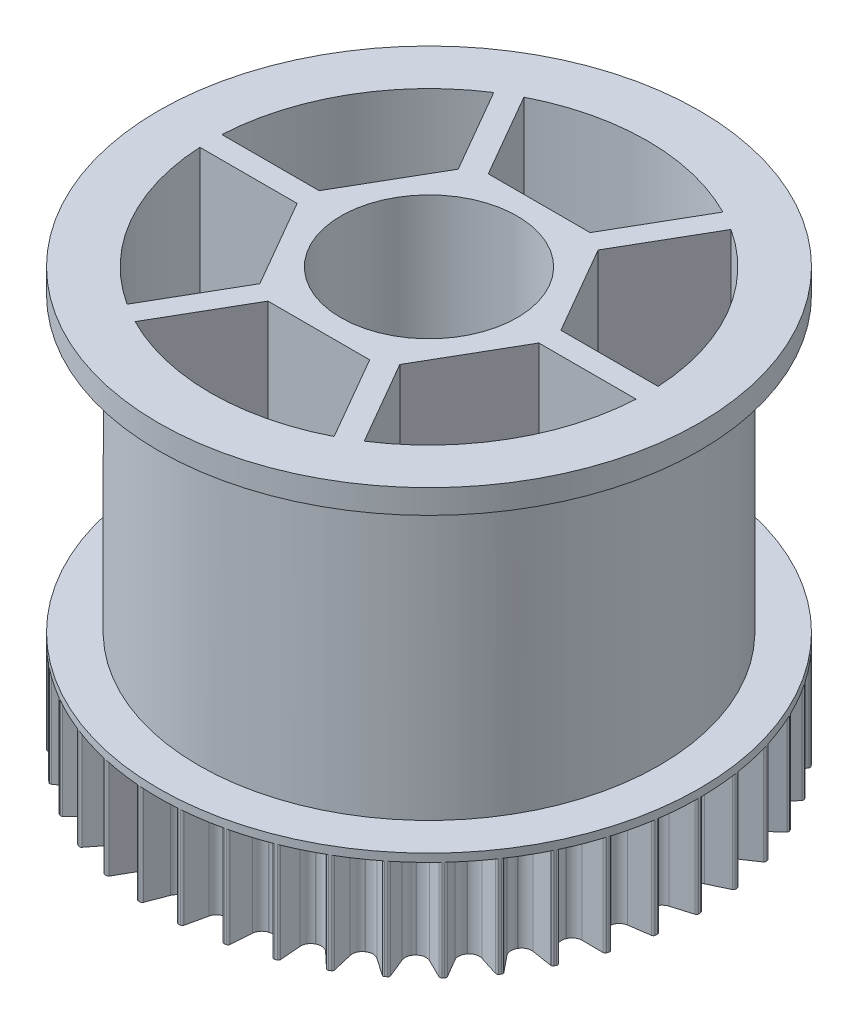
SolidWorks part; units mm, degrees
ref_plane "前视基准面" through (0, 0, 0) normal (0, 0, 1) x (1, 0, 0)
ref_plane "上视基准面" through (0, 0, 0) normal (0, 1, 0) x (1, 0, 0)
ref_plane "右视基准面" through (0, 0, 0) normal (1, 0, 0) x (0, 0, -1)
other "Configuration Table"
sketch "草图1" plane through (0, 0, 0) normal (0, 1, 0) x (1, 0, 0)
  line L0 (0, 0) -> (7.9279, 0) construction
  line L1 (0, 0) -> (0, 4.4256) construction
  line L2 (12.4216, 0.4494) -> (13.4287, 0.1463)
  line L3 (12.4216, -0.4494) -> (13.4287, -0.1463)
  line L4 (12.2159, -2.2957) -> (13.2569, -2.1461)
  line L5 (12.3499, -1.407) -> (13.3005, -1.8568)
  line L6 (11.7373, -4.0908) -> (12.789, -4.098)
  line L7 (12.0023, -3.2319) -> (12.8752, -3.8184)
  line L8 (10.9965, -5.7945) -> (12.0354, -5.9583)
  line L9 (11.3865, -4.9846) -> (12.1623, -5.6947)
  line L10 (10.0101, -7.3687) -> (11.0129, -7.6855)
  line L11 (10.5164, -6.626) -> (11.1777, -7.4438)
  line L12 (8.8, -8.7783) -> (9.7445, -9.2411)
  line L13 (9.4114, -8.1194) -> (9.9434, -9.0266)
  line L14 (7.3934, -9.9918) -> (8.2583, -10.5902)
  line L15 (8.0961, -9.4314) -> (8.487, -10.4078)
  line L16 (5.8216, -10.9822) -> (6.5877, -11.7028)
  line L17 (6.6, -10.5328) -> (6.841, -11.5565)
  line L18 (4.1198, -11.7272) -> (4.7699, -12.5539)
  line L19 (4.9565, -11.3988) -> (5.0422, -12.447)
  line L20 (2.3259, -12.2102) -> (2.8456, -13.1246)
  line L21 (3.2022, -12.0102) -> (3.1308, -13.0595)
  line L22 (0.4801, -12.4205) -> (0.8577, -13.4021)
  line L23 (1.3764, -12.3533) -> (1.1494, -13.3802)
  line L24 (-1.3764, -12.3533) -> (-1.1494, -13.3802)
  line L25 (-0.4801, -12.4205) -> (-0.8577, -13.4021)
  line L26 (-3.2022, -12.0102) -> (-3.1308, -13.0595)
  line L27 (-2.3259, -12.2102) -> (-2.8456, -13.1246)
  line L28 (-4.9565, -11.3988) -> (-5.0422, -12.447)
  line L29 (-4.1198, -11.7272) -> (-4.7699, -12.5539)
  line L30 (-6.6, -10.5328) -> (-6.841, -11.5565)
  line L31 (-5.8216, -10.9822) -> (-6.5877, -11.7028)
  line L32 (-8.0961, -9.4314) -> (-8.487, -10.4078)
  line L33 (-7.3934, -9.9918) -> (-8.2583, -10.5902)
  line L34 (-9.4114, -8.1194) -> (-9.9434, -9.0266)
  line L35 (-8.8, -8.7783) -> (-9.7445, -9.2411)
  line L36 (-10.5164, -6.626) -> (-11.1777, -7.4438)
  line L37 (-10.0101, -7.3687) -> (-11.0129, -7.6855)
  line L38 (-11.3865, -4.9846) -> (-12.1623, -5.6947)
  line L39 (-10.9965, -5.7945) -> (-12.0354, -5.9583)
  line L40 (-12.0023, -3.2319) -> (-12.8752, -3.8184)
  line L41 (-11.7373, -4.0908) -> (-12.789, -4.098)
  line L42 (-12.3499, -1.407) -> (-13.3005, -1.8568)
  line L43 (-12.2159, -2.2957) -> (-13.2569, -2.1461)
  line L44 (-12.4216, 0.4494) -> (-13.4287, 0.1463)
  line L45 (-12.4216, -0.4494) -> (-13.4287, -0.1463)
  line L46 (-12.2159, 2.2957) -> (-13.2569, 2.1461)
  line L47 (-12.3499, 1.407) -> (-13.3005, 1.8568)
  line L48 (-11.7373, 4.0908) -> (-12.789, 4.098)
  line L49 (-12.0023, 3.2319) -> (-12.8752, 3.8184)
  line L50 (-10.9965, 5.7945) -> (-12.0354, 5.9583)
  line L51 (-11.3865, 4.9846) -> (-12.1623, 5.6947)
  line L52 (-10.0101, 7.3687) -> (-11.0129, 7.6855)
  line L53 (-10.5164, 6.626) -> (-11.1777, 7.4438)
  line L54 (-8.8, 8.7783) -> (-9.7445, 9.2411)
  line L55 (-9.4114, 8.1194) -> (-9.9434, 9.0266)
  line L56 (-7.3934, 9.9918) -> (-8.2583, 10.5902)
  line L57 (-8.0961, 9.4314) -> (-8.487, 10.4078)
  line L58 (-5.8216, 10.9822) -> (-6.5877, 11.7028)
  line L59 (-6.6, 10.5328) -> (-6.841, 11.5565)
  line L60 (-4.1198, 11.7272) -> (-4.7699, 12.5539)
  line L61 (-4.9565, 11.3988) -> (-5.0422, 12.447)
  line L62 (-2.3259, 12.2102) -> (-2.8456, 13.1246)
  line L63 (-3.2022, 12.0102) -> (-3.1308, 13.0595)
  line L64 (-0.4801, 12.4205) -> (-0.8577, 13.4021)
  line L65 (-1.3764, 12.3533) -> (-1.1494, 13.3802)
  line L66 (1.3764, 12.3533) -> (1.1494, 13.3802)
  line L67 (0.4801, 12.4205) -> (0.8577, 13.4021)
  line L68 (3.2022, 12.0102) -> (3.1308, 13.0595)
  line L69 (2.3259, 12.2102) -> (2.8456, 13.1246)
  line L70 (4.9565, 11.3988) -> (5.0422, 12.447)
  line L71 (4.1198, 11.7272) -> (4.7699, 12.5539)
  line L72 (6.6, 10.5328) -> (6.841, 11.5565)
  line L73 (5.8216, 10.9822) -> (6.5877, 11.7028)
  line L74 (8.0961, 9.4314) -> (8.487, 10.4078)
  line L75 (7.3934, 9.9918) -> (8.2583, 10.5902)
  line L76 (9.4114, 8.1194) -> (9.9434, 9.0266)
  line L77 (8.8, 8.7783) -> (9.7445, 9.2411)
  line L78 (10.5164, 6.626) -> (11.1777, 7.4438)
  line L79 (10.0101, 7.3687) -> (11.0129, 7.6855)
  line L80 (11.3865, 4.9846) -> (12.1623, 5.6947)
  line L81 (10.9965, 5.7945) -> (12.0354, 5.9583)
  line L82 (12.0023, 3.2319) -> (12.8752, 3.8184)
  line L83 (11.7373, 4.0908) -> (12.789, 4.098)
  line L84 (12.3499, 1.407) -> (13.3005, 1.8568)
  line L85 (12.2159, 2.2957) -> (13.2569, 2.1461)
  line L95 (3.1754, 5.5) -> (-3.1754, 5.5) construction
  line L96 (3.1754, 5.5) -> (6.0333, 0.55) construction
  line L97 (0, 0) -> (3.1754, 5.5) construction
  line L98 (-3.1754, 5.5) -> (-6.0333, 0.55) construction
  line L99 (3.493, -4.95) -> (6.0333, -0.55)
  line L100 (2.5403, -5.5) -> (-2.5403, -5.5)
  line L101 (-3.493, -4.95) -> (-6.0333, -0.55)
  line L102 (8.1752, 0) -> (11.2, 0) construction
  line L103 (6.0333, 0.55) -> (11.1865, 0.55)
  line L104 (6.0333, -0.55) -> (11.1865, -0.55)
  line L105 (3.493, -4.95) -> (6.0696, -9.4128)
  line L106 (2.5403, -5.5) -> (5.1169, -9.9628)
  line L107 (-2.5403, -5.5) -> (-5.1169, -9.9628)
  line L108 (-3.493, -4.95) -> (-6.0696, -9.4128)
  line L109 (-6.0333, -0.55) -> (-11.1865, -0.55)
  line L110 (-6.0333, 0.55) -> (-11.1865, 0.55)
  line L111 (-3.493, 4.95) -> (-6.0696, 9.4128)
  line L112 (-2.5403, 5.5) -> (-5.1169, 9.9628)
  line L113 (2.5403, 5.5) -> (5.1169, 9.9628)
  line L114 (3.493, 4.95) -> (6.0696, 9.4128)
  line L115 (0, 0) -> (12.0337, 1.2648) construction
  line L116 (12.0337, -1.2648) -> (0, 0) construction
  line L117 (-6.0333, 0.55) -> (-3.493, 4.95)
  line L118 (-2.5403, 5.5) -> (2.5403, 5.5)
  line L119 (3.493, 4.95) -> (6.0333, 0.55)
  circle A0 centre (0, 0) radius 11.2 construction
  circle A1 centre (0, 0) radius 12.1 construction
  circle A2 centre (0, 0) radius 13.5 construction
  arc A3 (13.4999, 0.0509) -> (13.4999, -0.0509) centre (0, 0) cw
  arc A4 (12.0671, 0.8914) -> (12.0337, 1.2648) centre (0, 0) ccw construction
  arc A5 (13.4287, -0.1463) -> (13.4999, -0.0509) centre (13.3999, -0.0505) ccw
  arc A6 (13.4287, 0.1463) -> (13.4999, 0.0509) centre (13.3999, 0.0505) cw
  arc A7 (12.0671, -0.8914) -> (12.0337, -1.2648) centre (0, 0) cw construction
  arc A8 (12.4216, -0.4494) -> (12.0671, -0.8914) centre (12.5658, -0.9282) ccw
  arc A9 (12.4216, 0.4494) -> (12.0671, 0.8914) centre (12.5658, 0.9282) cw
  arc A10 (12.2159, -2.2957) -> (11.7995, -2.6799) centre (12.2871, -2.7907) ccw
  arc A11 (12.3499, -1.407) -> (12.0652, -0.9171) centre (12.5638, -0.955) cw
  arc A12 (13.3005, -1.8568) -> (13.3567, -1.9617) centre (13.2578, -1.9472) cw
  arc A13 (13.3567, -1.9617) -> (13.3415, -2.0624) centre (0, 0) cw
  arc A14 (13.2569, -2.1461) -> (13.3415, -2.0624) centre (13.2427, -2.0471) ccw
  arc A15 (11.7373, -4.0908) -> (11.2683, -4.4086) centre (11.7339, -4.5908) ccw
  arc A16 (12.0023, -3.2319) -> (11.7937, -2.7051) centre (12.2811, -2.8169) cw
  arc A17 (12.8752, -3.8184) -> (12.9151, -3.9305) centre (12.8195, -3.9014) cw
  arc A18 (12.9151, -3.9305) -> (12.8851, -4.0278) centre (0, 0) cw
  arc A19 (12.789, -4.098) -> (12.8851, -4.0278) centre (12.7897, -3.998) ccw
  arc A20 (10.9965, -5.7945) -> (10.4854, -6.0388) centre (10.9186, -6.2884) ccw
  arc A21 (11.3865, -4.9846) -> (11.2589, -4.4326) centre (11.7241, -4.6158) cw
  arc A22 (12.1623, -5.6947) -> (12.1851, -5.8115) centre (12.0948, -5.7685) cw
  arc A23 (12.1851, -5.8115) -> (12.1409, -5.9032) centre (0, 0) cw
  arc A24 (12.0354, -5.9583) -> (12.1409, -5.9032) centre (12.051, -5.8595) ccw
  arc A25 (10.0101, -7.3687) -> (9.4682, -7.5341) centre (9.8595, -7.8455) ccw
  arc A26 (10.5164, -6.626) -> (10.4724, -6.0612) centre (10.9052, -6.3116) cw
  arc A27 (11.1777, -7.4438) -> (11.1828, -7.5627) centre (11.1, -7.5067) cw
  arc A28 (11.1828, -7.5627) -> (11.1255, -7.6468) centre (0, 0) cw
  arc A29 (11.0129, -7.6855) -> (11.1255, -7.6468) centre (11.0431, -7.5902) ccw
  arc A30 (8.8, -8.7783) -> (8.2395, -8.8611) centre (8.58, -9.2273) ccw
  arc A31 (9.4114, -8.1194) -> (9.4521, -7.5543) centre (9.8427, -7.8665) cw
  arc A32 (9.9434, -9.0266) -> (9.9308, -9.145) centre (9.8572, -9.0772) cw
  arc A33 (9.9308, -9.145) -> (9.8615, -9.2196) centre (0, 0) cw
  arc A34 (9.7445, -9.2411) -> (9.8615, -9.2196) centre (9.7885, -9.1513) ccw
  arc A35 (7.3934, -9.9918) -> (6.8268, -9.9902) centre (7.1089, -10.403) ccw
  arc A36 (8.0961, -9.4314) -> (8.2206, -8.8787) centre (8.5603, -9.2456) cw
  arc A37 (8.487, -10.4078) -> (8.4568, -10.5229) centre (8.3942, -10.445) cw
  arc A38 (8.4568, -10.5229) -> (8.3773, -10.5864) centre (0, 0) cw
  arc A39 (8.2583, -10.5902) -> (8.3773, -10.5864) centre (8.3152, -10.508) ccw
  arc A40 (5.8216, -10.9822) -> (5.2616, -10.8961) centre (5.479, -11.3464) ccw
  arc A41 (6.6, -10.5328) -> (6.8055, -10.0048) centre (7.0867, -10.4182) cw
  arc A42 (6.841, -11.5565) -> (6.794, -11.6658) centre (6.7437, -11.5794) cw
  arc A43 (6.794, -11.6658) -> (6.7059, -11.7167) centre (0, 0) cw
  arc A44 (6.5877, -11.7028) -> (6.7059, -11.7167) centre (6.6562, -11.6299) ccw
  arc A45 (4.1198, -11.7272) -> (3.5789, -11.5586) centre (3.7268, -12.0362) ccw
  arc A46 (4.9565, -11.3988) -> (5.2384, -10.9073) centre (5.4548, -11.358) cw
  arc A47 (5.0422, -12.447) -> (4.9795, -12.5481) centre (4.9426, -12.4552) cw
  arc A48 (4.9795, -12.5481) -> (4.8847, -12.5853) centre (0, 0) cw
  arc A49 (4.7699, -12.5539) -> (4.8847, -12.5853) centre (4.8485, -12.4921) ccw
  arc A50 (2.3259, -12.2102) -> (1.8162, -11.9629) centre (1.8912, -12.4573) ccw
  arc A51 (3.2022, -12.0102) -> (3.5542, -11.5662) centre (3.7011, -12.0442) cw
  arc A52 (3.1308, -13.0595) -> (3.0536, -13.1501) centre (3.031, -13.0527) cw
  arc A53 (3.0536, -13.1501) -> (2.9544, -13.1728) centre (0, 0) cw
  arc A54 (2.8456, -13.1246) -> (2.9544, -13.1728) centre (2.9325, -13.0752) ccw
  arc A55 (0.4801, -12.4205) -> (0.0129, -12.1) centre (0.0134, -12.6) ccw
  arc A56 (1.3764, -12.3533) -> (1.7906, -11.9668) centre (1.8646, -12.4613) cw
  arc A57 (1.1494, -13.3802) -> (1.0596, -13.4584) centre (1.0518, -13.3587) cw
  arc A58 (1.0596, -13.4584) -> (0.9581, -13.466) centre (0, 0) cw
  arc A59 (0.8577, -13.4021) -> (0.9581, -13.466) centre (0.951, -13.3662) ccw
  arc A60 (-1.3764, -12.3533) -> (-1.7906, -11.9668) centre (-1.8646, -12.4613) ccw
  arc A61 (-0.4801, -12.4205) -> (-0.0129, -12.1) centre (-0.0134, -12.6) cw
  arc A62 (-0.8577, -13.4021) -> (-0.9581, -13.466) centre (-0.951, -13.3662) cw
  arc A63 (-0.9581, -13.466) -> (-1.0596, -13.4584) centre (0, 0) cw
  arc A64 (-1.1494, -13.3802) -> (-1.0596, -13.4584) centre (-1.0518, -13.3587) ccw
  arc A65 (-3.2022, -12.0102) -> (-3.5542, -11.5662) centre (-3.7011, -12.0442) ccw
  arc A66 (-2.3259, -12.2102) -> (-1.8162, -11.9629) centre (-1.8912, -12.4573) cw
  arc A67 (-2.8456, -13.1246) -> (-2.9544, -13.1728) centre (-2.9325, -13.0752) cw
  arc A68 (-2.9544, -13.1728) -> (-3.0536, -13.1501) centre (0, 0) cw
  arc A69 (-3.1308, -13.0595) -> (-3.0536, -13.1501) centre (-3.031, -13.0527) ccw
  arc A70 (-4.9565, -11.3988) -> (-5.2384, -10.9073) centre (-5.4548, -11.358) ccw
  arc A71 (-4.1198, -11.7272) -> (-3.5789, -11.5586) centre (-3.7268, -12.0362) cw
  arc A72 (-4.7699, -12.5539) -> (-4.8847, -12.5853) centre (-4.8485, -12.4921) cw
  arc A73 (-4.8847, -12.5853) -> (-4.9795, -12.5481) centre (0, 0) cw
  arc A74 (-5.0422, -12.447) -> (-4.9795, -12.5481) centre (-4.9426, -12.4552) ccw
  arc A75 (-6.6, -10.5328) -> (-6.8055, -10.0048) centre (-7.0867, -10.4182) ccw
  arc A76 (-5.8216, -10.9822) -> (-5.2616, -10.8961) centre (-5.479, -11.3464) cw
  arc A77 (-6.5877, -11.7028) -> (-6.7059, -11.7167) centre (-6.6562, -11.6299) cw
  arc A78 (-6.7059, -11.7167) -> (-6.794, -11.6658) centre (0, 0) cw
  arc A79 (-6.841, -11.5565) -> (-6.794, -11.6658) centre (-6.7437, -11.5794) ccw
  arc A80 (-8.0961, -9.4314) -> (-8.2206, -8.8787) centre (-8.5603, -9.2456) ccw
  arc A81 (-7.3934, -9.9918) -> (-6.8268, -9.9902) centre (-7.1089, -10.403) cw
  arc A82 (-8.2583, -10.5902) -> (-8.3773, -10.5864) centre (-8.3152, -10.508) cw
  arc A83 (-8.3773, -10.5864) -> (-8.4568, -10.5229) centre (0, 0) cw
  arc A84 (-8.487, -10.4078) -> (-8.4568, -10.5229) centre (-8.3942, -10.445) ccw
  arc A85 (-9.4114, -8.1194) -> (-9.4521, -7.5543) centre (-9.8427, -7.8665) ccw
  arc A86 (-8.8, -8.7783) -> (-8.2395, -8.8611) centre (-8.58, -9.2273) cw
  arc A87 (-9.7445, -9.2411) -> (-9.8615, -9.2196) centre (-9.7885, -9.1513) cw
  arc A88 (-9.8615, -9.2196) -> (-9.9308, -9.145) centre (0, 0) cw
  arc A89 (-9.9434, -9.0266) -> (-9.9308, -9.145) centre (-9.8572, -9.0772) ccw
  arc A90 (-10.5164, -6.626) -> (-10.4724, -6.0612) centre (-10.9052, -6.3116) ccw
  arc A91 (-10.0101, -7.3687) -> (-9.4682, -7.5341) centre (-9.8595, -7.8455) cw
  arc A92 (-11.0129, -7.6855) -> (-11.1255, -7.6468) centre (-11.0431, -7.5902) cw
  arc A93 (-11.1255, -7.6468) -> (-11.1828, -7.5627) centre (0, 0) cw
  arc A94 (-11.1777, -7.4438) -> (-11.1828, -7.5627) centre (-11.1, -7.5067) ccw
  arc A95 (-11.3865, -4.9846) -> (-11.2589, -4.4326) centre (-11.7241, -4.6158) ccw
  arc A96 (-10.9965, -5.7945) -> (-10.4854, -6.0388) centre (-10.9186, -6.2884) cw
  arc A97 (-12.0354, -5.9583) -> (-12.1409, -5.9032) centre (-12.051, -5.8595) cw
  arc A98 (-12.1409, -5.9032) -> (-12.1851, -5.8115) centre (0, 0) cw
  arc A99 (-12.1623, -5.6947) -> (-12.1851, -5.8115) centre (-12.0948, -5.7685) ccw
  arc A100 (-12.0023, -3.2319) -> (-11.7937, -2.7051) centre (-12.2811, -2.8169) ccw
  arc A101 (-11.7373, -4.0908) -> (-11.2683, -4.4086) centre (-11.7339, -4.5908) cw
  arc A102 (-12.789, -4.098) -> (-12.8851, -4.0278) centre (-12.7897, -3.998) cw
  arc A103 (-12.8851, -4.0278) -> (-12.9151, -3.9305) centre (0, 0) cw
  arc A104 (-12.8752, -3.8184) -> (-12.9151, -3.9305) centre (-12.8195, -3.9014) ccw
  arc A105 (-12.3499, -1.407) -> (-12.0652, -0.9171) centre (-12.5638, -0.955) ccw
  arc A106 (-12.2159, -2.2957) -> (-11.7995, -2.6799) centre (-12.2871, -2.7907) cw
  arc A107 (-13.2569, -2.1461) -> (-13.3415, -2.0624) centre (-13.2427, -2.0471) cw
  arc A108 (-13.3415, -2.0624) -> (-13.3567, -1.9617) centre (0, 0) cw
  arc A109 (-13.3005, -1.8568) -> (-13.3567, -1.9617) centre (-13.2578, -1.9472) ccw
  arc A110 (-12.4216, 0.4494) -> (-12.0671, 0.8914) centre (-12.5658, 0.9282) ccw
  arc A111 (-12.4216, -0.4494) -> (-12.0671, -0.8914) centre (-12.5658, -0.9282) cw
  arc A112 (-13.4287, -0.1463) -> (-13.4999, -0.0509) centre (-13.3999, -0.0505) cw
  arc A113 (-13.4999, -0.0509) -> (-13.4999, 0.0509) centre (0, 0) cw
  arc A114 (-13.4287, 0.1463) -> (-13.4999, 0.0509) centre (-13.3999, 0.0505) ccw
  arc A115 (-12.2159, 2.2957) -> (-11.7995, 2.6799) centre (-12.2871, 2.7907) ccw
  arc A116 (-12.3499, 1.407) -> (-12.0652, 0.9171) centre (-12.5638, 0.955) cw
  arc A117 (-13.3005, 1.8568) -> (-13.3567, 1.9617) centre (-13.2578, 1.9472) cw
  arc A118 (-13.3567, 1.9617) -> (-13.3415, 2.0624) centre (0, 0) cw
  arc A119 (-13.2569, 2.1461) -> (-13.3415, 2.0624) centre (-13.2427, 2.0471) ccw
  arc A120 (-11.7373, 4.0908) -> (-11.2683, 4.4086) centre (-11.7339, 4.5908) ccw
  arc A121 (-12.0023, 3.2319) -> (-11.7937, 2.7051) centre (-12.2811, 2.8169) cw
  arc A122 (-12.8752, 3.8184) -> (-12.9151, 3.9305) centre (-12.8195, 3.9014) cw
  arc A123 (-12.9151, 3.9305) -> (-12.8851, 4.0278) centre (0, 0) cw
  arc A124 (-12.789, 4.098) -> (-12.8851, 4.0278) centre (-12.7897, 3.998) ccw
  arc A125 (-10.9965, 5.7945) -> (-10.4854, 6.0388) centre (-10.9186, 6.2884) ccw
  arc A126 (-11.3865, 4.9846) -> (-11.2589, 4.4326) centre (-11.7241, 4.6158) cw
  arc A127 (-12.1623, 5.6947) -> (-12.1851, 5.8115) centre (-12.0948, 5.7685) cw
  arc A128 (-12.1851, 5.8115) -> (-12.1409, 5.9032) centre (0, 0) cw
  arc A129 (-12.0354, 5.9583) -> (-12.1409, 5.9032) centre (-12.051, 5.8595) ccw
  arc A130 (-10.0101, 7.3687) -> (-9.4682, 7.5341) centre (-9.8595, 7.8455) ccw
  arc A131 (-10.5164, 6.626) -> (-10.4724, 6.0612) centre (-10.9052, 6.3116) cw
  arc A132 (-11.1777, 7.4438) -> (-11.1828, 7.5627) centre (-11.1, 7.5067) cw
  arc A133 (-11.1828, 7.5627) -> (-11.1255, 7.6468) centre (0, 0) cw
  arc A134 (-11.0129, 7.6855) -> (-11.1255, 7.6468) centre (-11.0431, 7.5902) ccw
  arc A135 (-8.8, 8.7783) -> (-8.2395, 8.8611) centre (-8.58, 9.2273) ccw
  arc A136 (-9.4114, 8.1194) -> (-9.4521, 7.5543) centre (-9.8427, 7.8665) cw
  arc A137 (-9.9434, 9.0266) -> (-9.9308, 9.145) centre (-9.8572, 9.0772) cw
  arc A138 (-9.9308, 9.145) -> (-9.8615, 9.2196) centre (0, 0) cw
  arc A139 (-9.7445, 9.2411) -> (-9.8615, 9.2196) centre (-9.7885, 9.1513) ccw
  arc A140 (-7.3934, 9.9918) -> (-6.8268, 9.9902) centre (-7.1089, 10.403) ccw
  arc A141 (-8.0961, 9.4314) -> (-8.2206, 8.8787) centre (-8.5603, 9.2456) cw
  arc A142 (-8.487, 10.4078) -> (-8.4568, 10.5229) centre (-8.3942, 10.445) cw
  arc A143 (-8.4568, 10.5229) -> (-8.3773, 10.5864) centre (0, 0) cw
  arc A144 (-8.2583, 10.5902) -> (-8.3773, 10.5864) centre (-8.3152, 10.508) ccw
  arc A145 (-5.8216, 10.9822) -> (-5.2616, 10.8961) centre (-5.479, 11.3464) ccw
  arc A146 (-6.6, 10.5328) -> (-6.8055, 10.0048) centre (-7.0867, 10.4182) cw
  arc A147 (-6.841, 11.5565) -> (-6.794, 11.6658) centre (-6.7437, 11.5794) cw
  arc A148 (-6.794, 11.6658) -> (-6.7059, 11.7167) centre (0, 0) cw
  arc A149 (-6.5877, 11.7028) -> (-6.7059, 11.7167) centre (-6.6562, 11.6299) ccw
  arc A150 (-4.1198, 11.7272) -> (-3.5789, 11.5586) centre (-3.7268, 12.0362) ccw
  arc A151 (-4.9565, 11.3988) -> (-5.2384, 10.9073) centre (-5.4548, 11.358) cw
  arc A152 (-5.0422, 12.447) -> (-4.9795, 12.5481) centre (-4.9426, 12.4552) cw
  arc A153 (-4.9795, 12.5481) -> (-4.8847, 12.5853) centre (0, 0) cw
  arc A154 (-4.7699, 12.5539) -> (-4.8847, 12.5853) centre (-4.8485, 12.4921) ccw
  arc A155 (-2.3259, 12.2102) -> (-1.8162, 11.9629) centre (-1.8912, 12.4573) ccw
  arc A156 (-3.2022, 12.0102) -> (-3.5542, 11.5662) centre (-3.7011, 12.0442) cw
  arc A157 (-3.1308, 13.0595) -> (-3.0536, 13.1501) centre (-3.031, 13.0527) cw
  arc A158 (-3.0536, 13.1501) -> (-2.9544, 13.1728) centre (0, 0) cw
  arc A159 (-2.8456, 13.1246) -> (-2.9544, 13.1728) centre (-2.9325, 13.0752) ccw
  arc A160 (-0.4801, 12.4205) -> (-0.0129, 12.1) centre (-0.0134, 12.6) ccw
  arc A161 (-1.3764, 12.3533) -> (-1.7906, 11.9668) centre (-1.8646, 12.4613) cw
  arc A162 (-1.1494, 13.3802) -> (-1.0596, 13.4584) centre (-1.0518, 13.3587) cw
  arc A163 (-1.0596, 13.4584) -> (-0.9581, 13.466) centre (0, 0) cw
  arc A164 (-0.8577, 13.4021) -> (-0.9581, 13.466) centre (-0.951, 13.3662) ccw
  arc A165 (1.3764, 12.3533) -> (1.7906, 11.9668) centre (1.8646, 12.4613) ccw
  arc A166 (0.4801, 12.4205) -> (0.0129, 12.1) centre (0.0134, 12.6) cw
  arc A167 (0.8577, 13.4021) -> (0.9581, 13.466) centre (0.951, 13.3662) cw
  arc A168 (0.9581, 13.466) -> (1.0596, 13.4584) centre (0, 0) cw
  arc A169 (1.1494, 13.3802) -> (1.0596, 13.4584) centre (1.0518, 13.3587) ccw
  arc A170 (3.2022, 12.0102) -> (3.5542, 11.5662) centre (3.7011, 12.0442) ccw
  arc A171 (2.3259, 12.2102) -> (1.8162, 11.9629) centre (1.8912, 12.4573) cw
  arc A172 (2.8456, 13.1246) -> (2.9544, 13.1728) centre (2.9325, 13.0752) cw
  arc A173 (2.9544, 13.1728) -> (3.0536, 13.1501) centre (0, 0) cw
  arc A174 (3.1308, 13.0595) -> (3.0536, 13.1501) centre (3.031, 13.0527) ccw
  arc A175 (4.9565, 11.3988) -> (5.2384, 10.9073) centre (5.4548, 11.358) ccw
  arc A176 (4.1198, 11.7272) -> (3.5789, 11.5586) centre (3.7268, 12.0362) cw
  arc A177 (4.7699, 12.5539) -> (4.8847, 12.5853) centre (4.8485, 12.4921) cw
  arc A178 (4.8847, 12.5853) -> (4.9795, 12.5481) centre (0, 0) cw
  arc A179 (5.0422, 12.447) -> (4.9795, 12.5481) centre (4.9426, 12.4552) ccw
  arc A180 (6.6, 10.5328) -> (6.8055, 10.0048) centre (7.0867, 10.4182) ccw
  arc A181 (5.8216, 10.9822) -> (5.2616, 10.8961) centre (5.479, 11.3464) cw
  arc A182 (6.5877, 11.7028) -> (6.7059, 11.7167) centre (6.6562, 11.6299) cw
  arc A183 (6.7059, 11.7167) -> (6.794, 11.6658) centre (0, 0) cw
  arc A184 (6.841, 11.5565) -> (6.794, 11.6658) centre (6.7437, 11.5794) ccw
  arc A185 (8.0961, 9.4314) -> (8.2206, 8.8787) centre (8.5603, 9.2456) ccw
  arc A186 (7.3934, 9.9918) -> (6.8268, 9.9902) centre (7.1089, 10.403) cw
  arc A187 (8.2583, 10.5902) -> (8.3773, 10.5864) centre (8.3152, 10.508) cw
  arc A188 (8.3773, 10.5864) -> (8.4568, 10.5229) centre (0, 0) cw
  arc A189 (8.487, 10.4078) -> (8.4568, 10.5229) centre (8.3942, 10.445) ccw
  arc A190 (9.4114, 8.1194) -> (9.4521, 7.5543) centre (9.8427, 7.8665) ccw
  arc A191 (8.8, 8.7783) -> (8.2395, 8.8611) centre (8.58, 9.2273) cw
  arc A192 (9.7445, 9.2411) -> (9.8615, 9.2196) centre (9.7885, 9.1513) cw
  arc A193 (9.8615, 9.2196) -> (9.9308, 9.145) centre (0, 0) cw
  arc A194 (9.9434, 9.0266) -> (9.9308, 9.145) centre (9.8572, 9.0772) ccw
  arc A195 (10.5164, 6.626) -> (10.4724, 6.0612) centre (10.9052, 6.3116) ccw
  arc A196 (10.0101, 7.3687) -> (9.4682, 7.5341) centre (9.8595, 7.8455) cw
  arc A197 (11.0129, 7.6855) -> (11.1255, 7.6468) centre (11.0431, 7.5902) cw
  arc A198 (11.1255, 7.6468) -> (11.1828, 7.5627) centre (0, 0) cw
  arc A199 (11.1777, 7.4438) -> (11.1828, 7.5627) centre (11.1, 7.5067) ccw
  arc A200 (11.3865, 4.9846) -> (11.2589, 4.4326) centre (11.7241, 4.6158) ccw
  arc A201 (10.9965, 5.7945) -> (10.4854, 6.0388) centre (10.9186, 6.2884) cw
  arc A202 (12.0354, 5.9583) -> (12.1409, 5.9032) centre (12.051, 5.8595) cw
  arc A203 (12.1409, 5.9032) -> (12.1851, 5.8115) centre (0, 0) cw
  arc A204 (12.1623, 5.6947) -> (12.1851, 5.8115) centre (12.0948, 5.7685) ccw
  arc A205 (12.0023, 3.2319) -> (11.7937, 2.7051) centre (12.2811, 2.8169) ccw
  arc A206 (11.7373, 4.0908) -> (11.2683, 4.4086) centre (11.7339, 4.5908) cw
  arc A207 (12.789, 4.098) -> (12.8851, 4.0278) centre (12.7897, 3.998) cw
  arc A208 (12.8851, 4.0278) -> (12.9151, 3.9305) centre (0, 0) cw
  arc A209 (12.8752, 3.8184) -> (12.9151, 3.9305) centre (12.8195, 3.9014) ccw
  arc A210 (12.3499, 1.407) -> (12.0652, 0.9171) centre (12.5638, 0.955) ccw
  arc A211 (12.2159, 2.2957) -> (11.7995, 2.6799) centre (12.2871, 2.7907) cw
  arc A212 (13.2569, 2.1461) -> (13.3415, 2.0624) centre (13.2427, 2.0471) cw
  arc A213 (13.3415, 2.0624) -> (13.3567, 1.9617) centre (0, 0) cw
  arc A214 (13.3005, 1.8568) -> (13.3567, 1.9617) centre (13.2578, 1.9472) ccw
  circle A216 centre (0, 0) radius 4.4
  arc A217 (11.1865, 0.55) -> (6.0696, 9.4128) centre (0, 0) ccw
  arc A218 (5.1169, 9.9628) -> (-5.1169, 9.9628) centre (0, 0) ccw
  arc A219 (-6.0696, 9.4128) -> (-11.1865, 0.55) centre (0, 0) ccw
  arc A220 (-11.1865, -0.55) -> (-6.0696, -9.4128) centre (0, 0) ccw
  arc A221 (-5.1169, -9.9628) -> (5.1169, -9.9628) centre (0, 0) ccw
  arc A222 (6.0696, -9.4128) -> (11.1865, -0.55) centre (0, 0) ccw
  arc A223 (12.0652, 0.9171) -> (12.0671, 0.8914) centre (0, 0) cw
  arc A224 (12.0671, -0.8914) -> (12.0652, -0.9171) centre (0, 0) cw
  arc A225 (11.7995, -2.6799) -> (11.7937, -2.7051) centre (0, 0) cw
  arc A226 (11.2683, -4.4086) -> (11.2589, -4.4326) centre (0, 0) cw
  arc A227 (10.4854, -6.0388) -> (10.4724, -6.0612) centre (0, 0) cw
  arc A228 (9.4682, -7.5341) -> (9.4521, -7.5543) centre (0, 0) cw
  arc A229 (8.2395, -8.8611) -> (8.2206, -8.8787) centre (0, 0) cw
  arc A230 (6.8268, -9.9902) -> (6.8055, -10.0048) centre (0, 0) cw
  arc A231 (5.2616, -10.8961) -> (5.2384, -10.9073) centre (0, 0) cw
  arc A232 (3.5789, -11.5586) -> (3.5542, -11.5662) centre (0, 0) cw
  arc A233 (1.8162, -11.9629) -> (1.7906, -11.9668) centre (0, 0) cw
  arc A234 (0.0129, -12.1) -> (-0.0129, -12.1) centre (0, 0) cw
  arc A235 (-1.7906, -11.9668) -> (-1.8162, -11.9629) centre (0, 0) cw
  arc A236 (-3.5542, -11.5662) -> (-3.5789, -11.5586) centre (0, 0) cw
  arc A237 (-5.2384, -10.9073) -> (-5.2616, -10.8961) centre (0, 0) cw
  arc A238 (-6.8055, -10.0048) -> (-6.8268, -9.9902) centre (0, 0) cw
  arc A239 (-8.2206, -8.8787) -> (-8.2395, -8.8611) centre (0, 0) cw
  arc A240 (-9.4521, -7.5543) -> (-9.4682, -7.5341) centre (0, 0) cw
  arc A241 (-10.4724, -6.0612) -> (-10.4854, -6.0388) centre (0, 0) cw
  arc A242 (-11.2589, -4.4326) -> (-11.2683, -4.4086) centre (0, 0) cw
  arc A243 (-11.7937, -2.7051) -> (-11.7995, -2.6799) centre (0, 0) cw
  arc A244 (-12.0652, -0.9171) -> (-12.0671, -0.8914) centre (0, 0) cw
  arc A245 (-12.0671, 0.8914) -> (-12.0652, 0.9171) centre (0, 0) cw
  arc A246 (-11.7995, 2.6799) -> (-11.7937, 2.7051) centre (0, 0) cw
  arc A247 (-11.2683, 4.4086) -> (-11.2589, 4.4326) centre (0, 0) cw
  arc A248 (-10.4854, 6.0388) -> (-10.4724, 6.0612) centre (0, 0) cw
  arc A249 (-9.4682, 7.5341) -> (-9.4521, 7.5543) centre (0, 0) cw
  arc A250 (-8.2395, 8.8611) -> (-8.2206, 8.8787) centre (0, 0) cw
  arc A251 (-6.8268, 9.9902) -> (-6.8055, 10.0048) centre (0, 0) cw
  arc A252 (-5.2616, 10.8961) -> (-5.2384, 10.9073) centre (0, 0) cw
  arc A253 (-3.5789, 11.5586) -> (-3.5542, 11.5662) centre (0, 0) cw
  arc A254 (-1.8162, 11.9629) -> (-1.7906, 11.9668) centre (0, 0) cw
  arc A255 (-0.0129, 12.1) -> (0.0129, 12.1) centre (0, 0) cw
  arc A256 (1.7906, 11.9668) -> (1.8162, 11.9629) centre (0, 0) cw
  arc A257 (3.5542, 11.5662) -> (3.5789, 11.5586) centre (0, 0) cw
  arc A258 (5.2384, 10.9073) -> (5.2616, 10.8961) centre (0, 0) cw
  arc A259 (6.8055, 10.0048) -> (6.8268, 9.9902) centre (0, 0) cw
  arc A260 (8.2206, 8.8787) -> (8.2395, 8.8611) centre (0, 0) cw
  arc A261 (9.4521, 7.5543) -> (9.4682, 7.5341) centre (0, 0) cw
  arc A262 (10.4724, 6.0612) -> (10.4854, 6.0388) centre (0, 0) cw
  arc A263 (11.2589, 4.4326) -> (11.2683, 4.4086) centre (0, 0) cw
  arc A264 (11.7937, 2.7051) -> (11.7995, 2.6799) centre (0, 0) cw
  circle A265 centre (0, 0) radius 3.5
  point P17 (13.4994, -0.125)
  point P20 (13.4994, 0.125)
  point P23 (12.0875, -0.55)
  point P26 (12.0875, 0.55)
  point P524 (0, 5.5)
  dimension "D1" = 22.4
  dimension "D2" = 24.2
  dimension "D3" = 27
  dimension "D6" = 0.1
  dimension "D7" = 0.5
  dimension "D9" = 120
  dimension "D12" = 8.8
  dimension "D14" = 7
  dimension "D4" = 1.1
  dimension "D5" = 0.25
  dimension "D10" = 5.5
  dimension "D11" = 30
  dimension "D16" = 6
  dimension "D17" = 6
  dimension "D8" = 42
  dimension "D13" = 6
  dimension "D15" = 42
extrude "凸台-拉伸1" add sketch "草图1" along normal blind 5 contours A264 A205 L82 A209 A208 A207 L83 A206 A263 A200 L80 A204 A203 A202 L81 A201 A262 A195 L78 A199 A198 A197 L79 A196 A261 A190 L76 A194 A193 A192 L77 A191 A260 A185 L74 A189 A188 A187 L75 A186 A259 A180 L72 A184 A183 A182 L73 A181 A258 A175 L70 region at (12.8153, 0, 0.0673)
sketch "草图2" plane through (0, 5, 0) normal (0, 1, 0) x (1, 0, 0)
  circle A0 centre (0, 0) radius 13.5
  circle A2 centre (0, 0) radius 11.2
  arc A4 (11.1865, 0.55) -> (6.0696, 9.4128) centre (0, 0) ccw construction
  dimension "D1" = 27
extrude "凸台-拉伸2" add sketch "草图2" along normal blind 0.4 contours A0 A2 | A2 | A0 region at (-13.1182, 5, 0)
extrude "拉伸-薄壁2" add sketch "草图2<2>" along normal blind 15 thin contours A2 thin type mid plane wall 0.6
sketch "草图2<2>" plane through (0, 5, 0) normal (0, 1, 0) x (1, 0, 0) same geometry as "草图2"
sketch "草图5" plane through (0, 20, 0) normal (0, 1, 0) x (1, 0, 0)
  circle A0 centre (0, 0) radius 13.5
  circle A2 centre (0, 0) radius 10.9
  circle A3 centre (0, 0) radius 10.9 construction
  dimension "D1" = 27
extrude "凸台-拉伸3" add sketch "草图5" along normal blind 1.2
sketch "草图6" plane through (0, 5, 0) normal (0, 1, 0) x (1, 0, 0)
  line L18 (-4.9667, -9.7027) -> (-2.5403, -5.5)
  line L19 (-2.5403, -5.5) -> (2.5403, -5.5)
  line L20 (2.5403, -5.5) -> (4.9667, -9.7027)
  line L21 (5.9194, -9.1527) -> (3.493, -4.95)
  line L22 (3.493, -4.95) -> (6.0333, -0.55)
  line L23 (6.0333, -0.55) -> (10.8861, -0.55)
  line L24 (10.8861, 0.55) -> (6.0333, 0.55)
  line L25 (6.0333, 0.55) -> (3.493, 4.95)
  line L26 (3.493, 4.95) -> (5.9194, 9.1527)
  line L27 (4.9667, 9.7027) -> (2.5403, 5.5)
  line L28 (2.5403, 5.5) -> (-2.5403, 5.5)
  line L29 (-2.5403, 5.5) -> (-4.9667, 9.7027)
  line L30 (-5.9194, 9.1527) -> (-3.493, 4.95)
  line L31 (-3.493, 4.95) -> (-6.0333, 0.55)
  line L32 (-6.0333, 0.55) -> (-10.8861, 0.55)
  line L33 (-10.8861, -0.55) -> (-6.0333, -0.55)
  line L34 (-6.0333, -0.55) -> (-3.493, -4.95)
  line L35 (-3.493, -4.95) -> (-5.9194, -9.1527)
  line L36 (-4.9667, -9.7027) -> (-2.5403, -5.5)
  line L37 (-2.5403, -5.5) -> (2.5403, -5.5)
  line L38 (2.5403, -5.5) -> (4.9667, -9.7027)
  line L39 (5.9194, -9.1527) -> (3.493, -4.95)
  line L40 (3.493, -4.95) -> (6.0333, -0.55)
  line L41 (6.0333, -0.55) -> (10.8861, -0.55)
  line L42 (10.8861, 0.55) -> (6.0333, 0.55)
  line L43 (6.0333, 0.55) -> (3.493, 4.95)
  line L44 (3.493, 4.95) -> (5.9194, 9.1527)
  line L45 (4.9667, 9.7027) -> (2.5403, 5.5)
  line L46 (2.5403, 5.5) -> (-2.5403, 5.5)
  line L47 (-2.5403, 5.5) -> (-4.9667, 9.7027)
  line L48 (-5.9194, 9.1527) -> (-3.493, 4.95)
  line L49 (-3.493, 4.95) -> (-6.0333, 0.55)
  line L50 (-6.0333, 0.55) -> (-10.8861, 0.55)
  line L51 (-10.8861, -0.55) -> (-6.0333, -0.55)
  line L52 (-6.0333, -0.55) -> (-3.493, -4.95)
  line L53 (-3.493, -4.95) -> (-5.9194, -9.1527)
  circle A0 centre (0, 0) radius 4.4
  circle A1 centre (0, 0) radius 4.4 construction
  arc A6 (-5.9194, -9.1527) -> (-4.9667, -9.7027) centre (0, 0) ccw
  arc A7 (4.9667, -9.7027) -> (5.9194, -9.1527) centre (0, 0) ccw
  arc A8 (10.8861, -0.55) -> (10.8861, 0.55) centre (0, 0) ccw
  arc A9 (5.9194, 9.1527) -> (4.9667, 9.7027) centre (0, 0) ccw
  arc A10 (-4.9667, 9.7027) -> (-5.9194, 9.1527) centre (0, 0) ccw
  arc A11 (-10.8861, 0.55) -> (-10.8861, -0.55) centre (0, 0) ccw
  arc A12 (-5.9194, -9.1527) -> (-4.9667, -9.7027) centre (0, 0) ccw
  arc A13 (4.9667, -9.7027) -> (5.9194, -9.1527) centre (0, 0) ccw
  arc A14 (10.8861, -0.55) -> (10.8861, 0.55) centre (0, 0) ccw
  arc A15 (5.9194, 9.1527) -> (4.9667, 9.7027) centre (0, 0) ccw
  arc A16 (-4.9667, 9.7027) -> (-5.9194, 9.1527) centre (0, 0) ccw
  arc A17 (-10.8861, 0.55) -> (-10.8861, -0.55) centre (0, 0) ccw
  dimension "D1" = 0
extrude "凸台-拉伸4" add sketch "草图6" along normal blind 8
extrude "凸台-拉伸5" add sketch "草图1<6>" along normal up to surface (13 mm away) contours A216 A265 region at (-4.2755, 0, 0) up to face at (0, 13, 0)
sketch "草图1<6>" plane through (0, 0, 0) normal (0, 1, 0) x (1, 0, 0) same geometry as "草图1"
extrude "切除-拉伸1" cut sketch "草图1<7>" along normal blind 3 contours A216 A265 region at (-4.2755, 0, 0)
sketch "草图1<7>" plane through (0, 0, 0) normal (0, 1, 0) x (1, 0, 0) same geometry as "草图1"
sketch "草图8" plane through (0, 13, 0) normal (0, 1, 0) x (1, 0, 0)
  circle A0 centre (0, 0) radius 4.4
  circle A1 centre (0, 0) radius 3.5
  circle A4 centre (0, 0) radius 3.5 construction
  dimension "D1" = 8.8
extrude "切除-拉伸2" cut sketch "草图8" against normal blind 3
sketch "草图14" plane through (0, 13, 0) normal (0, 1, 0) x (1, 0, 0)
  line L18 (-4.9667, -9.7027) -> (-2.5403, -5.5)
  line L19 (-2.5403, -5.5) -> (2.5403, -5.5)
  line L20 (2.5403, -5.5) -> (4.9667, -9.7027)
  line L21 (5.9194, -9.1527) -> (3.493, -4.95)
  line L22 (3.493, -4.95) -> (6.0333, -0.55)
  line L23 (6.0333, -0.55) -> (10.8861, -0.55)
  line L24 (10.8861, 0.55) -> (6.0333, 0.55)
  line L25 (6.0333, 0.55) -> (3.493, 4.95)
  line L26 (3.493, 4.95) -> (5.9194, 9.1527)
  line L27 (4.9667, 9.7027) -> (2.5403, 5.5)
  line L28 (2.5403, 5.5) -> (-2.5403, 5.5)
  line L29 (-2.5403, 5.5) -> (-4.9667, 9.7027)
  line L30 (-5.9194, 9.1527) -> (-3.493, 4.95)
  line L31 (-3.493, 4.95) -> (-6.0333, 0.55)
  line L32 (-6.0333, 0.55) -> (-10.8861, 0.55)
  line L33 (-10.8861, -0.55) -> (-6.0333, -0.55)
  line L34 (-6.0333, -0.55) -> (-3.493, -4.95)
  line L35 (-3.493, -4.95) -> (-5.9194, -9.1527)
  line L36 (-4.9667, -9.7027) -> (-2.5403, -5.5)
  line L37 (-2.5403, -5.5) -> (2.5403, -5.5)
  line L38 (2.5403, -5.5) -> (4.9667, -9.7027)
  line L39 (5.9194, -9.1527) -> (3.493, -4.95)
  line L40 (3.493, -4.95) -> (6.0333, -0.55)
  line L41 (6.0333, -0.55) -> (10.8861, -0.55)
  line L42 (10.8861, 0.55) -> (6.0333, 0.55)
  line L43 (6.0333, 0.55) -> (3.493, 4.95)
  line L44 (3.493, 4.95) -> (5.9194, 9.1527)
  line L45 (4.9667, 9.7027) -> (2.5403, 5.5)
  line L46 (2.5403, 5.5) -> (-2.5403, 5.5)
  line L47 (-2.5403, 5.5) -> (-4.9667, 9.7027)
  line L48 (-5.9194, 9.1527) -> (-3.493, 4.95)
  line L49 (-3.493, 4.95) -> (-6.0333, 0.55)
  line L50 (-6.0333, 0.55) -> (-10.8861, 0.55)
  line L51 (-10.8861, -0.55) -> (-6.0333, -0.55)
  line L52 (-6.0333, -0.55) -> (-3.493, -4.95)
  line L53 (-3.493, -4.95) -> (-5.9194, -9.1527)
  circle A0 centre (0, 0) radius 4.4 construction
  circle A1 centre (0, 0) radius 4.4
  arc A6 (-5.9194, -9.1527) -> (-4.9667, -9.7027) centre (0, 0) ccw
  arc A7 (4.9667, -9.7027) -> (5.9194, -9.1527) centre (0, 0) ccw
  arc A8 (10.8861, -0.55) -> (10.8861, 0.55) centre (0, 0) ccw
  arc A9 (5.9194, 9.1527) -> (4.9667, 9.7027) centre (0, 0) ccw
  arc A10 (-4.9667, 9.7027) -> (-5.9194, 9.1527) centre (0, 0) ccw
  arc A11 (-10.8861, 0.55) -> (-10.8861, -0.55) centre (0, 0) ccw
  arc A12 (-5.9194, -9.1527) -> (-4.9667, -9.7027) centre (0, 0) ccw
  arc A13 (4.9667, -9.7027) -> (5.9194, -9.1527) centre (0, 0) ccw
  arc A14 (10.8861, -0.55) -> (10.8861, 0.55) centre (0, 0) ccw
  arc A15 (5.9194, 9.1527) -> (4.9667, 9.7027) centre (0, 0) ccw
  arc A16 (-4.9667, 9.7027) -> (-5.9194, 9.1527) centre (0, 0) ccw
  arc A17 (-10.8861, 0.55) -> (-10.8861, -0.55) centre (0, 0) ccw
  dimension "D1" = 0
extrude "凸台-拉伸9" add sketch "草图14" along normal up to surface (8.2 mm away) up to face at (0, 21.2, 13.5)
